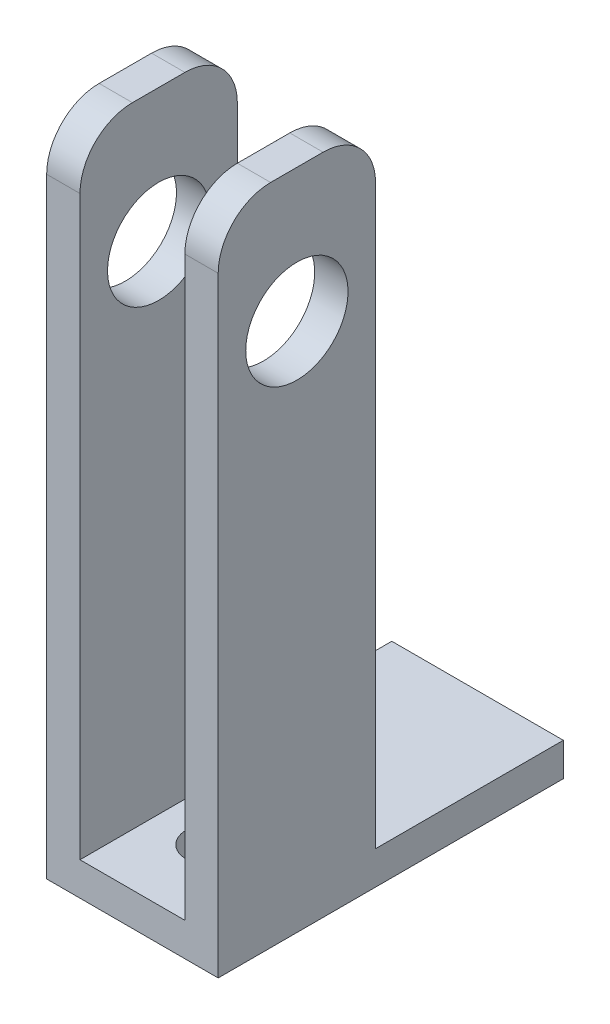
SolidWorks part; units mm, degrees
ref_plane "Front Plane" through (0, 0, 0) normal (0, 0, 1) x (1, 0, 0)
ref_plane "Top Plane" through (0, 0, 0) normal (0, 1, 0) x (1, 0, 0)
ref_plane "Right Plane" through (0, 0, 0) normal (1, 0, 0) x (0, 0, -1)
sketch "Sketch1" plane through (0, 0, 0) normal (0, 1, 0) x (1, 0, 0)
  circle A0 centre (0, 0) radius 10
  dimension "D1" = 20
extrude "Boss-Extrude1" add sketch "Sketch1" along normal blind 6.35
sketch "Sketch5" plane through (0, 6.35, 0) normal (0, 1, 0) x (1, 0, 0)
  line L27 (0, 15) -> (0, -15) construction
  line L28 (-10, 15) -> (10, 15)
  line L29 (-10, 15) -> (-10, -15)
  line L30 (-10, -15) -> (10, -15)
  line L31 (10, 15) -> (10, -15)
  line L32 (-10, 0) -> (10, 0) construction
  point P0 (0, 0)
  dimension "D1" = 20
  dimension "D2" = 30
extrude "Boss-Extrude2" add sketch "Sketch5" against normal blind 6.35
sketch "Sketch7" plane through (0, 6.35, 0) normal (0, 1, 0) x (1, 0, 0)
  line L13 (0, 0) -> (0, 21) construction
  line L29 (-16.35, 15) -> (-10, 15)
  line L30 (-16.35, 15) -> (-16.35, -15)
  line L31 (-16.35, -15) -> (-10, -15)
  line L32 (-10, 15) -> (-10, -15)
  line L38 (10, 15) -> (10, -15)
  line L39 (16.35, -15) -> (10, -15)
  line L40 (16.35, 15) -> (16.35, -15)
  line L41 (16.35, 15) -> (10, 15)
  circle A0 centre (0, 0) radius 38 construction
  dimension "D1" = 6.35
  dimension "D2" = 30
extrude "Boss-Extrude3" add sketch "Sketch7" along normal blind 120 and the other way blind 6.35
sketch "Sketch8" plane through (-16.35, 0, 0) normal (-1, 0, 0) x (0, 0, 1)
  line L4 (-15, 126.35) -> (15, 126.35) construction
  line L5 (0, 126.35) -> (0, 0) construction
  line L6 (-15, 126.35) -> (15, 126.35) construction
  line L7 (-15, 0) -> (15, 0) construction
  circle A0 centre (0, 100.95) radius 9.75
  dimension "D1" = 19.5
  dimension "D2" = 25.4
extrude "Cut-Extrude2" cut sketch "Sketch8" against normal through all
sketch "Sketch2" plane through (0, 6.35, 0) normal (0, 1, 0) x (1, 0, 0)
  circle A0 centre (0, 0) radius 4.7625
  dimension "D1" = 9.525
extrude "Cut-Extrude1" cut sketch "Sketch2" against normal through all
fillet "Fillet2" radius 10 4 edges at (13.175, 126.35, -15) (-13.175, 126.35, 15) (13.175, 126.35, 15) (-13.175, 126.35, -15)
sketch "Sketch11" plane through (0, 0, 0) normal (0, -1, 0) x (1, 0, 0)
  line L1 (-16.35, -15) -> (16.35, -15)
  line L2 (-16.35, -15) -> (-16.35, -50.8)
  line L3 (-16.35, -50.8) -> (16.35, -50.8)
  line L4 (16.35, -15) -> (16.35, -50.8)
  dimension "D1" = 35.8
extrude "Boss-Extrude5" add sketch "Sketch11" against normal blind 6.35
